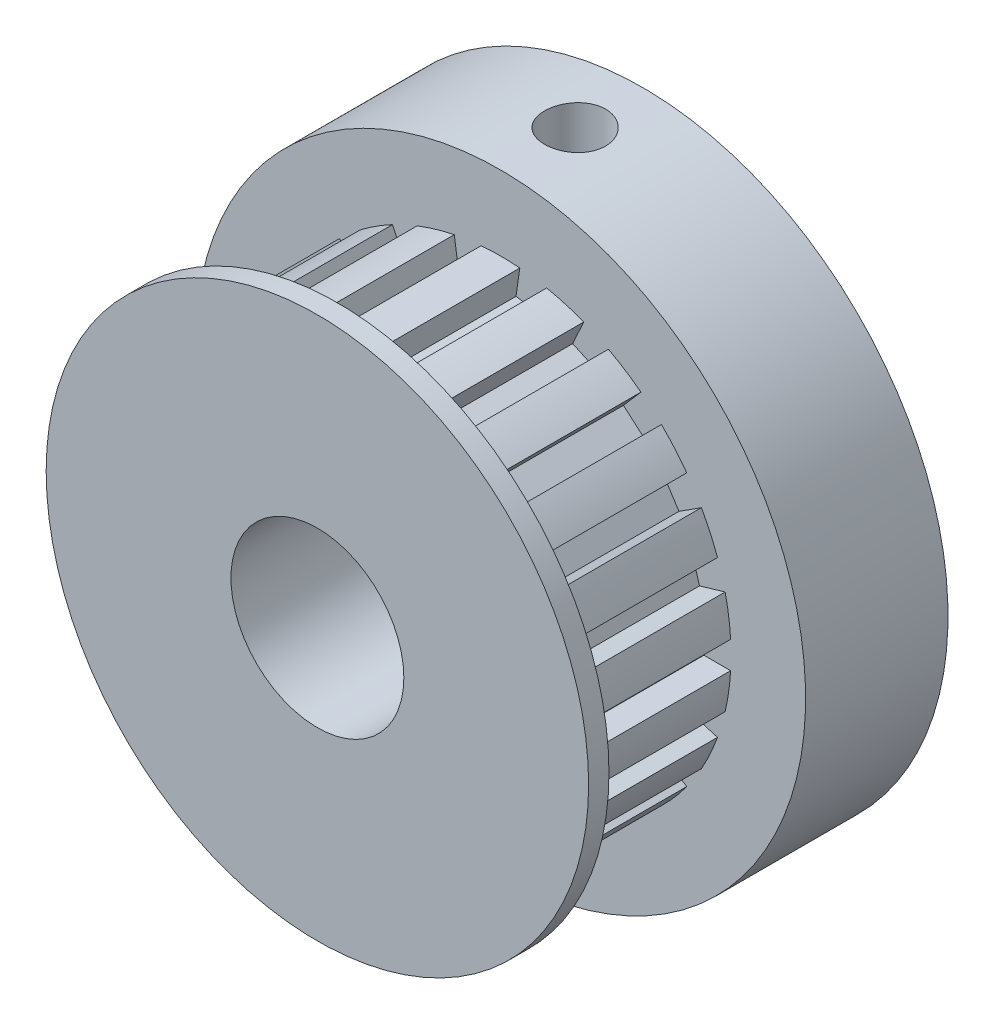
SolidWorks part; units mm, degrees
ref_plane "Front Plane" through (0, 0, 0) normal (0, 0, 1) x (1, 0, 0)
ref_plane "Top Plane" through (0, 0, 0) normal (0, 1, 0) x (1, 0, 0)
ref_plane "Right Plane" through (0, 0, 0) normal (1, 0, 0) x (0, 0, -1)
sketch "Sketch1" plane through (0, 0, 0) normal (0, 0, 1) x (1, 0, 0)
  circle A0 centre (0, 0) radius 10.16
  dimension "D1" = 20.32
extrude "Boss-Extrude1" add sketch "Sketch1" against normal blind 0.762
sketch "Sketch2" plane through (0, 0, -0.762) normal (0, 0, -1) x (-1, 0, 0)
  circle A0 centre (0, 0) radius 8.636
  dimension "D1" = 17.272
extrude "Boss-Extrude2" add sketch "Sketch2" along normal blind 6.096
sketch "Sketch3" plane through (0, 0, -6.858) normal (0, 0, -1) x (-1, 0, 0)
  circle A0 centre (0, 0) radius 11.43
  dimension "D1" = 22.86
extrude "Boss-Extrude3" add sketch "Sketch3" along normal blind 5.334
sketch "Sketch4" plane through (0, 0, 0) normal (0, 0, 1) x (1, 0, 0)
  circle A0 centre (0, 0) radius 3.2385
  dimension "D1" = 6.477
extrude "Cut-Extrude1" cut sketch "Sketch4" against normal blind 25.654
ref_plane "Plane2" through (-8.636, 0, 0) normal (-1, 0, 0) x (0, 0, 1)
sketch "Sketch5" plane through (-8.636, 0, 0) normal (-1, 0, 0) x (0, 0, 1)
  line L0 (-6.858, -8.636) -> (-6.858, 8.636) construction
  line L1 (-6.858, 0.508) -> (-0.762, 0.508)
  line L2 (-6.858, 0.508) -> (-6.858, -0.508)
  line L3 (-6.858, -0.508) -> (-0.762, -0.508)
  line L4 (-0.762, 0.508) -> (-0.762, -0.508)
  line L5 (-0.762, 8.636) -> (-0.762, -8.636) construction
  point P8 (-6.858, 0)
  dimension "D1" = 1.016
extrude "Cut-Extrude2" cut sketch "Sketch5" against normal blind 1.016
ref_axis "Axis1" through (0, 0, -12.192) along (0, 0, 1)
pattern_circular "CirPattern1" count 22 over 360 about axis through (0, 0, -12.192) along (0, 0, 1) of "Cut-Extrude2"
sketch "Sketch6" plane through (0, 0, 0) normal (0, 1, 0) x (1, 0, 0)
  line L0 (11.43, 12.192) -> (-11.43, 12.192) construction
  circle A0 centre (0, 9.652) radius 1.143
  dimension "D1" = 2.286
  dimension "D2" = 2.54
extrude "Cut-Extrude3" cut sketch "Sketch6" against normal blind 22.098 and the other way blind 22.098
